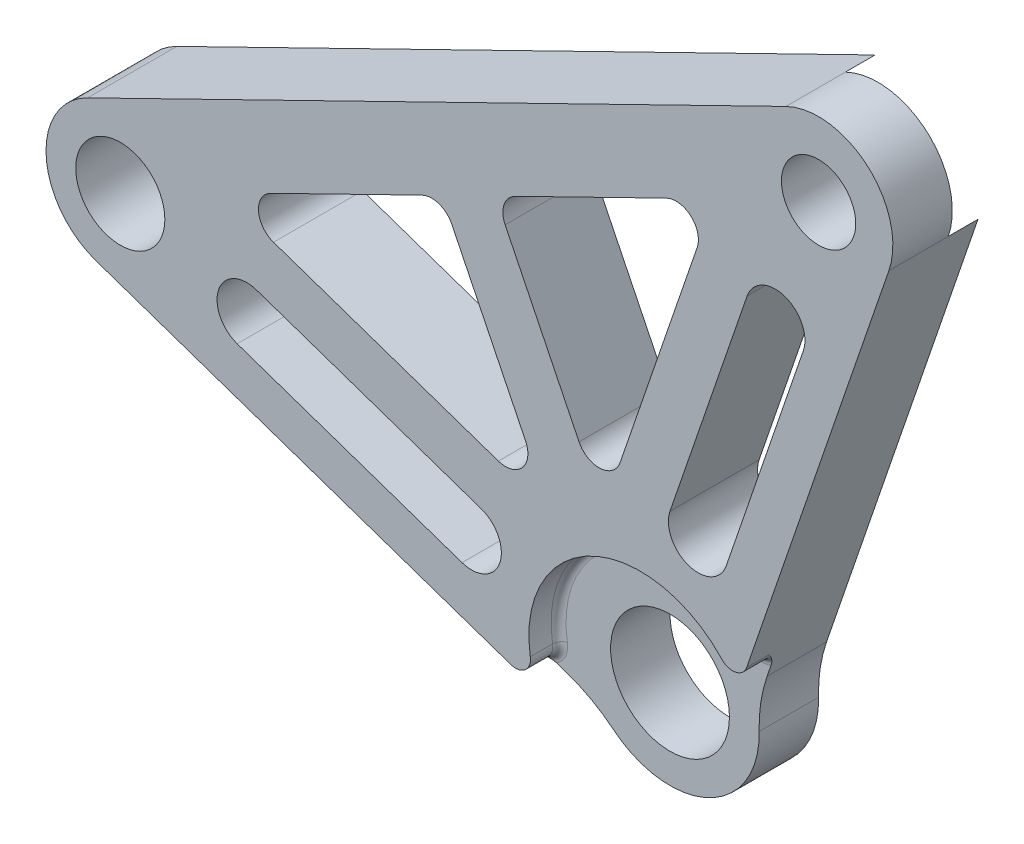
SolidWorks part; units mm, degrees
material "AISI 1045 Steel, cold drawn"
ref_plane "Front Plane" through (0, 0, 0) normal (0, 0, 1) x (1, 0, 0)
ref_plane "Top Plane" through (0, 0, 0) normal (0, 1, 0) x (1, 0, 0)
ref_plane "Right Plane" through (0, 0, 0) normal (1, 0, 0) x (0, 0, -1)
sketch "Sketch1" plane through (0, 0, 0) normal (0, 0, 1) x (1, 0, 0)
  line L2 (0, 0) -> (-35, 12) construction
  line L3 (0, 32.1948) -> (0, -15.8001) construction
  line L4 (16.7297, 33.3784) -> (6.5355, 3.6452)
  line L5 (0, 0) -> (12, 35) construction
  line L6 (-36.6216, 7.2703) -> (-6.8884, -2.924)
  line L7 (9.8022, 39.4911) -> (-37.1978, 16.4911)
  circle A1 centre (-35, 12) radius 3
  arc A2 (-37.1978, 16.4911) -> (-36.6216, 7.2703) centre (-35, 12) ccw
  circle A3 centre (0, 0) radius 4
  arc A5 (-6.8884, -2.924) -> (-3.7994, -4.6438) centre (-10.1317, -12.3834) cw
  circle A6 centre (12, 35) radius 2.5
  arc A7 (-3.7994, -4.6438) -> (5.9981, 0.1507) centre (0, 0) ccw
  arc A8 (5.9981, 0.1507) -> (6.5355, 3.6452) centre (15.995, 0.4019) cw
  arc A9 (16.7297, 33.3784) -> (9.8022, 39.4911) centre (12, 35) ccw
  dimension "D4" = 6
  dimension "D6" = 8
  dimension "D10" = 5
  dimension "D13" = 6
  dimension "D15" = 5
  dimension "D5" = 5
  dimension "D7" = 10
  dimension "D8" = 10
  dimension "D3" = 35
  dimension "D9" = 12
  dimension "D2" = 35
  dimension "D11" = 12
extrude "Boss-Extrude1" add sketch "Sketch1" along normal blind 6 contours A1 | A3 | A6 | L7 A2 L6 A5 A7 A8 L4 A9 region at (-35, 12, 0) region at (0, 0, 0) region at (12, 35, 0)
sketch "Sketch2" plane through (0, 0, 6) normal (0, 0, 1) x (1, 0, 0)
  line L0 (-24.8592, 17.0976) -> (-14.6971, 22.0705)
  line L1 (-12.6904, 21.3825) -> (-7.7175, 11.2204)
  line L2 (-9.5513, 9.1421) -> (-24.6864, 14.3313)
  line L3 (0, 0) -> (-17.0487, 34.8386) construction
  line L4 (-26.4865, 9.0811) -> (-11.3514, 3.8919) construction
  line L5 (9.8022, 39.4911) -> (-37.1978, 16.4911) construction
  line L6 (-25.8378, 10.973) -> (-10.7027, 5.7838)
  line L7 (-33.1957, 11.3814) -> (1.8043, -0.6186) construction
  line L8 (-36.6216, 7.2703) -> (-6.8884, -2.924) construction
  line L12 (-27.1351, 7.1892) -> (-12, 2)
  line L13 (-25.5935, 11.6856) -> (-19.6733, 28.9527) construction
  line L14 (-10.4555, 6.5048) -> (-3.0085, 28.2253) construction
  line L15 (-9.0976, 23.1408) -> (-4.1246, 12.9786)
  line L16 (1.7526, 30.1204) -> (-8.4096, 25.1474)
  line L17 (-1.3583, 13.1514) -> (3.8308, 28.2866)
  line L18 (9.0811, 26.4865) -> (3.8919, 11.3514) construction
  line L19 (7.1892, 27.1351) -> (2, 12)
  line L20 (10.973, 25.8378) -> (5.7838, 10.7027)
  arc A0 (-7.7175, 11.2204) -> (-9.5513, 9.1421) centre (-9.0648, 10.561) cw
  arc A1 (-24.8592, 17.0976) -> (-24.6864, 14.3313) centre (-24.1999, 15.7502) ccw
  arc A2 (-14.6971, 22.0705) -> (-12.6904, 21.3825) centre (-14.0378, 20.7232) cw
  arc A6 (-25.8378, 10.973) -> (-27.1351, 7.1892) centre (-26.4865, 9.0811) ccw
  arc A7 (-12, 2) -> (-10.7027, 5.7838) centre (-11.3514, 3.8919) ccw
  arc A8 (-8.4096, 25.1474) -> (-9.0976, 23.1408) centre (-7.7502, 23.8001) ccw
  arc A9 (-4.1246, 12.9786) -> (-1.3583, 13.1514) centre (-2.7773, 13.6379) ccw
  arc A10 (1.7526, 30.1204) -> (3.8308, 28.2866) centre (2.4119, 28.7731) cw
  arc A11 (7.1892, 27.1351) -> (10.973, 25.8378) centre (9.0811, 26.4865) cw
  arc A12 (5.7838, 10.7027) -> (2, 12) centre (3.8919, 11.3514) cw
  point P8 (-13.6978, 27.9911)
  point P17 (-18.9189, 6.4865)
  point P41 (6.4865, 18.9189)
  dimension "D4" = 1.5
  dimension "D3" = 2
  dimension "D1" = 2
  dimension "D2" = 12
  dimension "D5" = 16
extrude "Cut-Extrude1" cut sketch "Sketch2" against normal through all both and the other way through all
sketch "Sketch4" plane through (0, 0, 6) normal (0, 0, 1) x (1, 0, 0)
  circle A0 centre (0, 0) radius 7.5
  circle A1 centre (-35, 12) radius 5
  circle A2 centre (-35, 12) radius 3 construction
  arc A3 (-37.1978, 16.4911) -> (-36.6216, 7.2703) centre (-35, 12) ccw construction
  point P10 (0, 0)
  dimension "D1" = 15
extrude "Cut-Extrude2" cut sketch "Sketch4" against normal blind 2 contours A0
fillet "Fillet1" radius 1 2 edges at (6.5428, 3.6664, 5) (-6.9096, -2.9167, 5)
fillet "Fillet2" radius 0.5 3 edges at (-7.7476, -2.1161, 4) (-3.2966, 6.7366, 4) (6.4248, 4.8193, 4)
sketch "Sketch5" plane through (0, 0, 0) normal (0, 0, -1) x (-1, 0, 0)
  circle A0 centre (-12, 35) radius 5
  point P3 (0, 0)
  point P4 (0, 0)
  point P5 (-12, 35)
  dimension "D1" = 10
extrude "Cut-Extrude4" cut sketch "Sketch5" against normal blind 2 contours A0
equation "\"D4@Sketch1\"=6"
equation "\"D5@Sketch1\"=\"D15@Sketch1\""
equation "\"D8@Sketch1\"=\"D7@Sketch1\""
